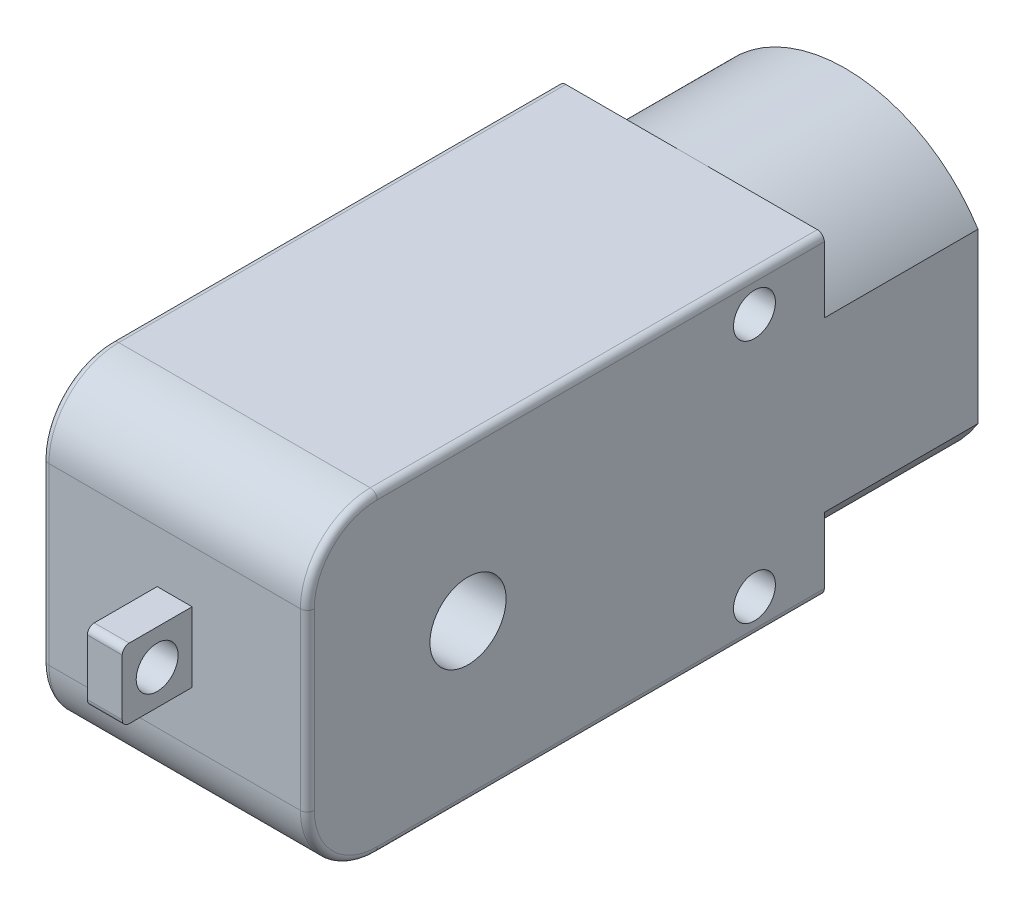
SolidWorks part; units mm, degrees
ref_plane "Front Plane" through (0, 0, 0) normal (0, 0, 1) x (1, 0, 0)
ref_plane "Top Plane" through (0, 0, 0) normal (0, 1, 0) x (1, 0, 0)
ref_plane "Right Plane" through (0, 0, 0) normal (1, 0, 0) x (0, 0, -1)
sketch "Sketch1" plane through (0, 0, 0) normal (0, 0, 1) x (1, 0, 0)
  line L1 (9.5, 11.25) -> (-9.5, 11.25)
  line L2 (9.5, 11.25) -> (9.5, -11.25)
  line L3 (9.5, -11.25) -> (-9.5, -11.25)
  line L4 (-9.5, 11.25) -> (-9.5, -11.25)
  line L5 (9.5, 11.25) -> (-9.5, -11.25) construction
  line L6 (9.5, -11.25) -> (-9.5, 11.25) construction
  point P0 (0, 0)
  dimension "D1" = 22.5
  dimension "D2" = 19
extrude "Boss-Extrude1" add sketch "Sketch1" along normal blind 37
sketch "Sketch2" plane through (0, 0, 0) normal (0, 0, -1) x (-1, 0, 0)
  line L0 (9.5, 6.026) -> (9.5, -6.026)
  line L1 (9.5, 11.25) -> (9.5, -11.25) construction
  line L2 (-9.5, 6.026) -> (-9.5, -6.026)
  arc A0 (9.5, 6.026) -> (-9.5, 6.026) centre (0, 0) ccw
  arc A1 (-9.5, -6.026) -> (9.5, -6.026) centre (0, 0) ccw
extrude "Boss-Extrude2" add sketch "Sketch2" along normal blind 11
fillet "Fillet1" radius 5 2 edges at (0, -11.25, 37) (0, 11.25, 37)
sketch "Sketch3" plane through (9.5, 0, 0) normal (1, 0, 0) x (0, 0, -1)
  circle A0 centre (-5, 8.75) radius 1.5
  circle A1 centre (-5, -8.75) radius 1.5
  dimension "D1" = 17.5
  dimension "D3" = 3
  dimension "D2" = 8.75
  dimension "D4" = 5
  dimension "D5" = 0
extrude "Cut-Extrude1" cut sketch "Sketch3" against normal through all
sketch "Sketch4" plane through (0, 0, 37) normal (0, 0, 1) x (1, 0, 0)
  line L1 (1.25, 2.5) -> (-1.25, 2.5)
  line L2 (1.25, 2.5) -> (1.25, -2.5)
  line L3 (1.25, -2.5) -> (-1.25, -2.5)
  line L4 (-1.25, 2.5) -> (-1.25, -2.5)
  line L5 (1.25, 2.5) -> (-1.25, -2.5) construction
  line L6 (1.25, -2.5) -> (-1.25, 2.5) construction
  point P0 (0, 0)
  dimension "D1" = 2.5
  dimension "D2" = 5
extrude "Boss-Extrude3" add sketch "Sketch4" along normal blind 5
fillet "Fillet2" radius 0.5 12 edges at (0, -2.5, 42) (0, 2.5, 42) (-9.5, -11.25, 16) (-9.5, -9.7855, 35.5355) (-9.5, 0, 37) (-9.5, 9.7855, 35.5355) (9.5, -11.25, 16) (9.5, -9.7855, 35.5355) (9.5, 0, 37) (9.5, 9.7855, 35.5355) (-9.5, 11.25, 16) (9.5, 11.25, 16)
sketch "Sketch5" plane through (1.25, 0, 0) normal (1, 0, 0) x (0, 0, -1)
  line L0 (-41.5, 2.5) -> (-37, 2.5) construction
  line L1 (-42, -2) -> (-42, 2) construction
  circle A0 centre (-39.5, 0) radius 1.5
  dimension "D1" = 3
  dimension "D2" = 2.5
  dimension "D3" = 2.5
extrude "Cut-Extrude2" cut sketch "Sketch5" against normal blind 5
sketch "Sketch6" plane through (9.5, 0, 0) normal (1, 0, 0) x (0, 0, -1)
  circle A0 centre (-25.5, 0) radius 2.725
  dimension "D1" = 5.45
  dimension "D2" = 25.5
extrude "Cut-Extrude3" cut sketch "Sketch6" against normal through all
sketch "Sketch7" plane through (0, 0, -11) normal (0, 0, -1) x (-1, 0, 0)
  line L4 (-8.3, 5.6668) -> (-8.3, -5.6668)
  line L5 (8.3, -5.6668) -> (8.3, 5.6668)
  line L6 (-8.3, 5.6668) -> (-8.3, -5.6668)
  line L7 (8.3, -5.6668) -> (8.3, 5.6668)
  arc A4 (8.3, 5.6668) -> (-8.3, 5.6668) centre (0, 0) ccw
  arc A5 (-8.3, -5.6668) -> (8.3, -5.6668) centre (0, 0) ccw
  arc A6 (8.3, 5.6668) -> (-8.3, 5.6668) centre (0, 0) ccw
  arc A7 (-8.3, -5.6668) -> (8.3, -5.6668) centre (0, 0) ccw
  dimension "D1" = 1.2
extrude "Cut-Extrude4" cut sketch "Sketch7" against normal blind 11
sketch "Sketch8" plane through (0, 0, 0) normal (0, 0, -1) x (-1, 0, 0)
  circle A0 centre (0, 0) radius 3
  dimension "D1" = 6
extrude "Cut-Extrude5" cut sketch "Sketch8" against normal blind 2
